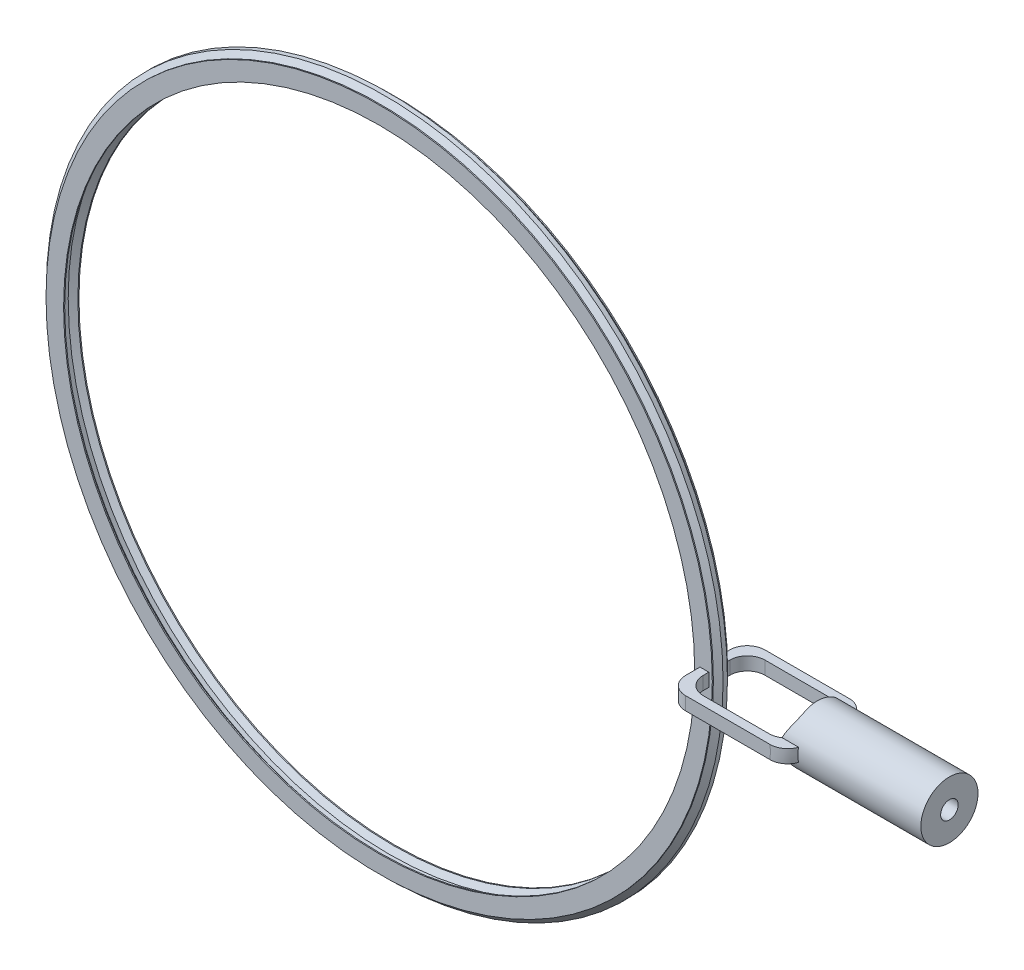
SolidWorks part; units mm, degrees
ref_plane "Front Plane" through (0, 0, 0) normal (0, 0, 1) x (1, 0, 0)
ref_plane "Top Plane" through (0, 0, 0) normal (0, 1, 0) x (1, 0, 0)
ref_plane "Right Plane" through (0, 0, 0) normal (1, 0, 0) x (0, 0, -1)
sketch "Sketch1" plane through (0, 0, 0) normal (1, 0, 0) x (0, 0, -1)
  line L0 (-1.75, 71.8) -> (-1.5, 71.8)
  line L1 (-1.5, 71.8) -> (-0.5, 73)
  line L2 (-0.5, 73) -> (0.5, 73)
  line L3 (0.5, 73) -> (1.5, 71.8)
  line L4 (1.5, 71.8) -> (1.75, 71.8)
  line L5 (1.75, 71.8) -> (1.75, 75.8)
  line L6 (1.75, 75.8) -> (1.5, 75.8)
  line L7 (1.5, 75.8) -> (0.5, 77)
  line L8 (0.5, 77) -> (-0.5, 77)
  line L9 (-0.5, 77) -> (-1.5, 75.8)
  line L10 (-1.5, 75.8) -> (-1.75, 75.8)
  line L11 (-1.75, 75.8) -> (-1.75, 71.8)
  line L12 (0, 0) -> (50000, 0) construction
  point P2 (0, 73)
  point P13 (0, 77)
  dimension "D1" = 0.25
  dimension "D2" = 1
  dimension "D3" = 3.5
  dimension "D4" = 0.25
  dimension "D5" = 1
  dimension "D6" = 1.2
  dimension "D7" = 1.2
  dimension "D8" = 4
  dimension "D9" = 73
revolve "Revolve1" add sketch "Sketch1" angle 360 about L12
sketch "Sketch2" plane through (0, 0, 0) normal (0, 1, 0) x (1, 0, 0)
  line L0 (74, 1.0247) -> (74, 8.0247)
  line L1 (74, 8.0247) -> (99, 8.0247)
  line L2 (99, 8.0247) -> (99, 4.0247)
  line L3 (74, -1.0247) -> (74, -8.0247)
  line L4 (74, -8.0247) -> (99, -8.0247)
  line L5 (99, -8.0247) -> (99, -4.0247)
  line L6 (74, 1.0247) -> (74, -1.0247) construction
  line L7 (0, -200000) -> (0, 250000) construction
  point P7 (74, 0)
  dimension "D1" = 25
  dimension "D2" = 7
  dimension "D3" = 4
  dimension "D4" = 74
extrude "Extrude-Thin1" add sketch "Sketch2" along normal mid plane 3 thin thin type mid plane wall 2
sketch "Sketch3" plane through (98, 0, 0) normal (1, 0, 0) x (0, 0, -1)
  circle A0 centre (0, 0) radius 6.5
  circle A1 centre (0, 0) radius 2
  dimension "D1" = 13
  dimension "D2" = 4
extrude "Boss-Extrude1" add sketch "Sketch3" along normal blind 30 contours A0
extrude "Cut-Extrude1" cut sketch "Sketch3<3>" against normal offset from surface 5 and the other way through all from surface contours A1 up to face at (98, 0, 0) starting at face at (128, 0, -6.5)
sketch "Sketch3<3>" plane through (98, 0, 0) normal (1, 0, 0) x (0, 0, -1) same geometry as "Sketch3"
fillet "Fillet2" radius 4 8 edges at (73, 0, -9.0247) (73, 0, 9.0247) (100, 0, 9.0247) (100, 0, -9.0247) (98, 0, 7.0247) (75, 0, 7.0247) (98, 0, -7.0247) (75, 0, -7.0247)
